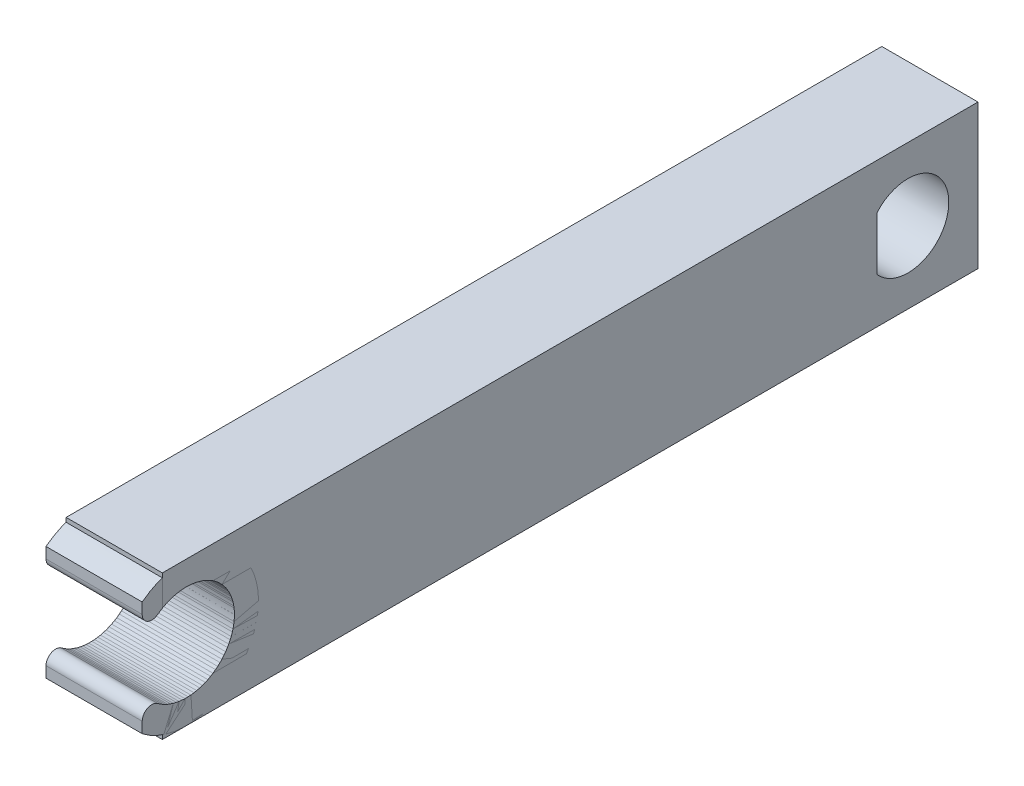
SolidWorks part; units mm, degrees
note: The reader was unsure of these and kept them because the rebuilt part matched: shared geometry of "草图2<3>".
ref_plane "前视基准面" through (0, 0, 0) normal (0, 0, 1) x (1, 0, 0)
ref_plane "上视基准面" through (0, 0, 0) normal (0, 1, 0) x (1, 0, 0)
ref_plane "右视基准面" through (0, 0, 0) normal (1, 0, 0) x (0, 0, -1)
sketch "草图1" plane through (0, 0, 0) normal (0, 0, 1) x (1, 0, 0)
  line L1 (-10.406, -12.3317) -> (-2.406, -12.3317)
  line L2 (-10.406, -12.3317) -> (-10.406, -24.3317)
  line L3 (-10.406, -24.3317) -> (-2.406, -24.3317)
  line L4 (-2.406, -12.3317) -> (-2.406, -24.3317)
extrude "凸台-拉伸1" add sketch "草图1" along normal blind 82
sketch "草图2" plane through (-10.406, 0, 0) normal (-1, 0, 0) x (0, 0, 1)
  line L0 (82, -18.3317) -> (80, -18.3317)
  line L1 (82, -12.3317) -> (82, -24.3317) construction
  circle A0 centre (80, -18.3317) radius 4
  circle A1 centre (80, -18.3317) radius 6
extrude "凸台-拉伸2" add sketch "草图2" against normal blind 8 separate body
sketch "草图3" plane through (-10.406, 0, 0) normal (-1, 0, 0) x (0, 0, 1)
  line L2 (83.6742, -12.3317) -> (83.6742, -43.5071)
  line L3 (83.6742, -43.5071) -> (128.4068, -43.5071)
  line L4 (128.4068, -12.3317) -> (128.4068, -43.5071)
  line L6 (83.6742, -12.3317) -> (83.6742, -1.6169)
  line L7 (83.6742, -1.6169) -> (128.4068, -1.6169)
  line L8 (128.4068, -12.3317) -> (128.4068, -1.6169)
extrude "切除-拉伸1" cut sketch "草图3" against normal blind 44
extrude "切除-拉伸2" cut sketch "草图2<3>" against normal blind 8
sketch "草图2<3>" plane through (-10.406, 0, 0) normal (-1, 0, 0) x (0, 0, 1) same geometry as "草图2"
fillet "圆角2" radius 0.8 2 edges at (-6.406, -19.913, 83.6742) (-6.406, -16.7504, 83.6742)
sketch "草图5" plane through (-10.406, 0, 0) normal (-1, 0, 0) x (0, 0, 1)
  line L0 (0, -18.3317) -> (20, -18.3317)
  line L1 (0, -12.3317) -> (0, -24.3317) construction
  line L2 (82, -24.3317) -> (0, -24.3317) construction
  line L3 (0, -12.3317) -> (14.172, -12.3317)
  line L4 (0, -12.3317) -> (0, -24.3317)
  line L5 (0, -24.3317) -> (14.172, -24.3317)
  line L6 (14.172, -12.3317) -> (14.172, -24.3317)
  line L7 (22.5559, -16.0896) -> (22.5559, -20.5739)
  circle A0 centre (20, -18.3317) radius 3.4
extrude "切除-拉伸3" cut sketch "草图5" against normal blind 10
